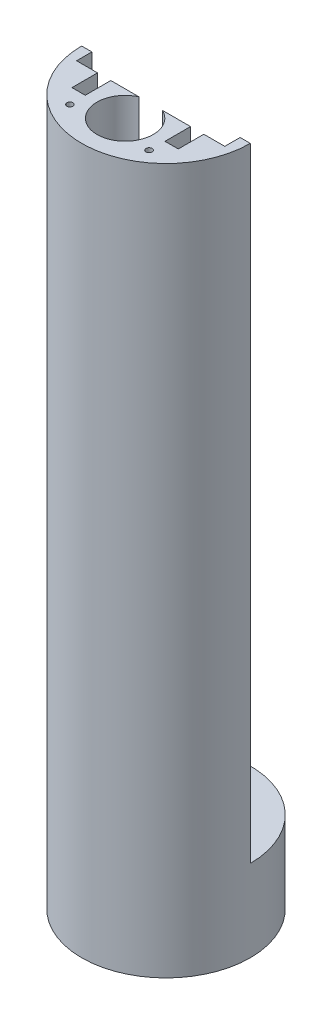
SolidWorks part; units mm, degrees
ref_plane "前视基准面" through (0, 0, 0) normal (0, 0, 1) x (1, 0, 0)
ref_plane "上视基准面" through (0, 0, 0) normal (0, 1, 0) x (1, 0, 0)
ref_plane "右视基准面" through (0, 0, 0) normal (1, 0, 0) x (0, 0, -1)
other "Configuration Table"
sketch "草图1" plane through (0, 0, 0) normal (0, 1, 0) x (1, 0, 0)
  circle A0 centre (0, 0) radius 16.5
  circle A1 centre (0, 0) radius 15.5
  dimension "D1" = 33
  dimension "D2" = 31
extrude "凸台-拉伸1" add sketch "草图1" along normal blind 6 contours A0
sketch "草图2" plane through (0, 6, 0) normal (0, 1, 0) x (1, 0, 0)
  line L0 (0, 0) -> (0, -8) construction
  line L1 (0, 5.1) -> (0, -1.9) construction
  line L2 (-6.1, -14.1) -> (6.1, -14.1)
  line L3 (-6.1, -14.1) -> (-6.1, -1.9)
  line L4 (-6.1, -1.9) -> (6.1, -1.9)
  line L5 (6.1, -14.1) -> (6.1, -1.9)
  line L6 (-6.1, -14.1) -> (6.1, -1.9) construction
  line L7 (-6.1, -1.9) -> (6.1, -14.1) construction
  line L8 (1.6, -1.9) -> (-1.6, -1.9)
  line L9 (1.6, -1.9) -> (1.6, 5.1)
  line L10 (1.6, 5.1) -> (-1.6, 5.1)
  line L11 (-1.6, -1.9) -> (-1.6, 5.1)
  circle A0 centre (0, -8) radius 4.25
  dimension "D1" = 8.5
  dimension "D2" = 8
  dimension "D3" = 12.2
  dimension "D4" = 3.2
  dimension "D5" = 7
extrude "切除-拉伸1" cut sketch "草图2" against normal through all contours A0
sketch "草图3" plane through (0, 0, 0) normal (0, -1, 0) x (1, 0, 0)
  circle A0 centre (-8.4853, 8.4853) radius 0.6
  circle A1 centre (8.4853, 8.4853) radius 0.6
  circle A2 centre (8.4853, -8.4853) radius 0.6
  circle A3 centre (-8.4853, -8.4853) radius 0.6
  dimension "D1" = 1.2
extrude "切除-拉伸2" cut sketch "草图3" against normal blind 3
sketch "草图4" plane through (0, 6, 0) normal (0, 1, 0) x (1, 0, 0)
  circle A0 centre (0, -8) radius 5.5
  circle A1 centre (0, -8) radius 4.25 construction
  circle M2 centre (0, 0) radius 16.5
  dimension "D1" = 11
extrude "凸台-拉伸2" add sketch "草图4" along normal blind 10 contours A0 M2 region at (0, 6, -1)
sketch "草图5" plane through (0, 16, 0) normal (0, 1, 0) x (1, 0, 0)
  line L0 (16.5, 0) -> (-16.5, 0)
  circle A0 centre (0, 0) radius 16.5 construction
  circle M2 centre (0, -8) radius 5.5
  circle M3 centre (0, 0) radius 16.5
extrude "凸台-拉伸3" add sketch "草图5" along normal blind 122 contours L0 M3 M2 region at (0, 16, 16.131)
sketch "草图6" plane through (0, 0, 0) normal (0, 0, -1) x (-1, 0, 0)
  line L0 (-16.5, 138) -> (16.5, 138) construction
  line L1 (-14.5, 138) -> (14.5, 138)
  line L2 (-14.5, 138) -> (-14.5, 105)
  line L3 (-14.5, 105) -> (14.5, 105)
  line L4 (14.5, 138) -> (14.5, 105)
  line L5 (0, 0) -> (0, 105) construction
  line L6 (-16.5, 0) -> (16.5, 0) construction
  line L7 (0, 92) -> (0, 105) construction
  line L8 (-1, 105) -> (1, 105)
  line L9 (-1, 105) -> (-1, 92)
  line L10 (-1, 92) -> (1, 92)
  line L11 (1, 105) -> (1, 92)
  dimension "D1" = 29
  dimension "D2" = 33
  dimension "D3" = 2
  dimension "D4" = 13
extrude "切除-拉伸3" cut sketch "草图6" against normal blind 3 contours L3 L4 L1 L2 | L11 L10 L9 L8
sketch "草图7" plane through (0, 0, 3) normal (0, 0, -1) x (-1, 0, 0)
  line L0 (1, 105) -> (14.5, 105) construction
  line L1 (7.8, 138) -> (10.4, 138)
  line L2 (7.8, 138) -> (7.8, 105)
  line L3 (7.8, 105) -> (10.4, 105)
  line L4 (10.4, 138) -> (10.4, 105)
  line L5 (-10.4, 138) -> (-7.8, 138)
  line L6 (-10.4, 138) -> (-10.4, 105)
  line L7 (-10.4, 105) -> (-7.8, 105)
  line L8 (-7.8, 138) -> (-7.8, 105)
  line L9 (-7.8, 138) -> (7.8, 138) construction
  line L10 (0, 138) -> (0, 0) construction
  line L11 (2.2913, 138) -> (14.5, 138) construction
  dimension "D1" = 2.6
  dimension "D2" = 15.6
extrude "切除-拉伸4" cut sketch "草图7" against normal blind 5
sketch "草图8" plane through (0, 0, 3) normal (0, 0, -1) x (-1, 0, 0)
  line L0 (-14.5, 133) -> (-10.4, 133) construction
  line L1 (-14.5, 138) -> (-14.5, 105) construction
  line L2 (-10.4, 138) -> (-10.4, 105) construction
  line L3 (-14.5, 138) -> (-10.4, 138) construction
  line L4 (10.4, 110) -> (14.5, 110) construction
  line L5 (10.4, 105) -> (10.4, 138) construction
  line L6 (14.5, 138) -> (14.5, 105) construction
  line L7 (1, 105) -> (14.5, 105) construction
  circle A0 centre (-12.45, 133) radius 0.4
  circle A1 centre (-12.45, 110) radius 0.4
  circle A2 centre (12.45, 133) radius 0.4
  circle A3 centre (12.45, 110) radius 0.4
  dimension "D2" = 0.8
  dimension "D1" = 5
  dimension "D3" = 5
extrude "切除-拉伸5" cut sketch "草图8" against normal blind 2
sketch "草图9" plane through (0, 0, 0) normal (0, 0, -1) x (-1, 0, 0)
  line L0 (0, 50.5) -> (0, 16) construction
  line L1 (0, 70.5) -> (0, 105) construction
  line L2 (-14.5, 105) -> (-1, 105) construction
  line L4 (16.5, 16) -> (-16.5, 16) construction
  circle A0 centre (0, 70.5) radius 0.6
  circle A1 centre (0, 50.5) radius 0.6
  dimension "D2" = 1.2
  dimension "D1" = 20
extrude "切除-拉伸6" cut sketch "草图9" against normal blind 2
sketch "草图10" plane through (0, 0, 0) normal (0, 0, -1) x (-1, 0, 0)
  line L0 (-16.5, 138) -> (-16.5, 16) construction
  line L1 (16.5, 138) -> (16.5, 16) construction
  line L3 (16.5, 16) -> (-16.5, 16) construction
  line L4 (-14.5, 105) -> (-1, 105) construction
  circle A0 centre (-6.5, 90) radius 0.6
  circle A1 centre (6.5, 90) radius 0.6
  circle A2 centre (6.5, 31) radius 0.6
  circle A3 centre (-6.5, 31) radius 0.6
  dimension "D1" = 1.2
  dimension "D2" = 10
  dimension "D3" = 10
  dimension "D4" = 15
  dimension "D5" = 15
extrude "切除-拉伸7" cut sketch "草图10" against normal blind 3
sketch "草图11" plane through (0, 138, 0) normal (0, 1, 0) x (1, 0, 0)
  line L0 (7.7433, -11.0586) -> (0, 0) construction
  line L1 (1, 0) -> (-1, 0) construction
  line L2 (0, 0) -> (-7.7433, -11.0586) construction
  line L3 (0, 0) -> (0, -15.0826) construction
  circle A0 centre (7.7433, -11.0586) radius 0.6
  circle A1 centre (-7.7433, -11.0586) radius 0.6
  dimension "D3" = 1.2
  dimension "D1" = 35
  dimension "D2" = 35
  dimension "D4" = 13.5
extrude "切除-拉伸8" cut sketch "草图11" against normal blind 3
sketch "草图12" plane through (0, 0, 0) normal (0, -1, 0) x (-1, 0, 0)
  circle A0 centre (0, 0) radius 1.5
  point P2 (-2.7686, -0.3214)
  point P4 (0, 0)
  dimension "D1" = 3
extrude "切除-拉伸9" cut sketch "草图12" against normal blind 40
